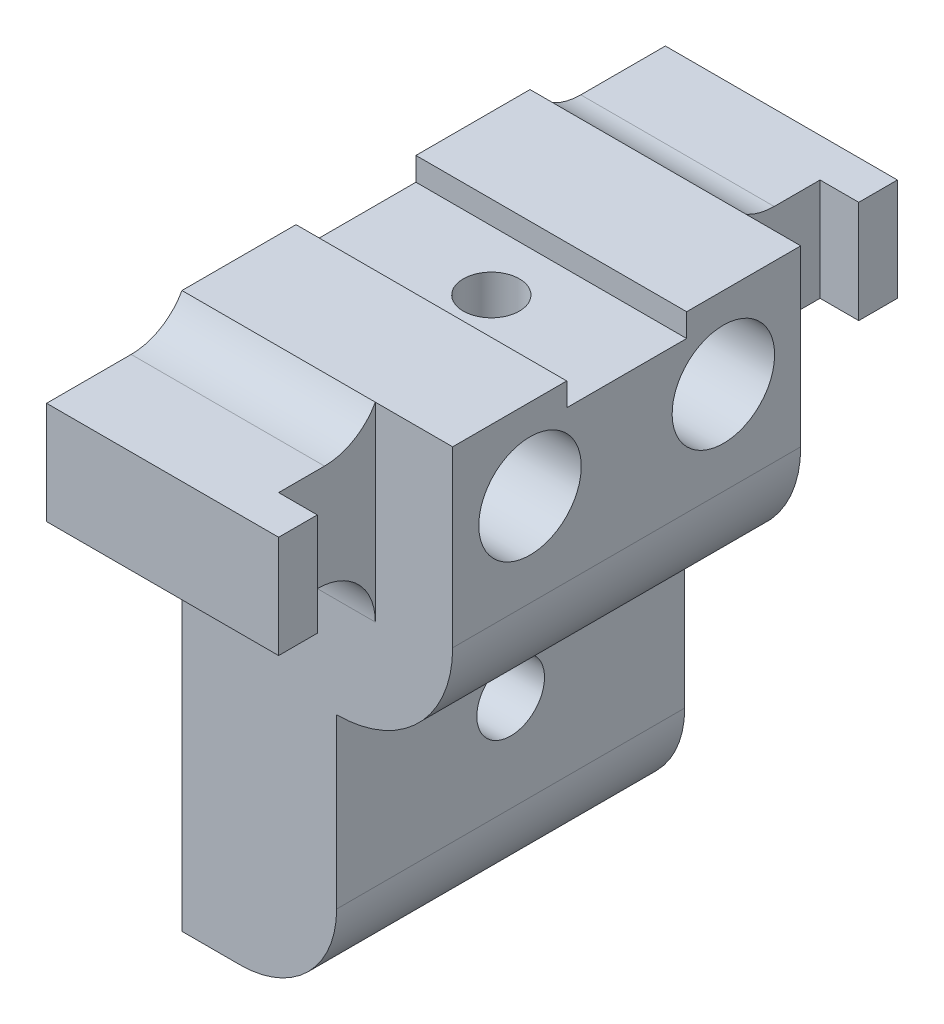
SolidWorks part; units mm, degrees
ref_plane "Front Plane" through (0, 0, 0) normal (0, 0, 1) x (1, 0, 0)
ref_plane "Top Plane" through (0, 0, 0) normal (0, 1, 0) x (1, 0, 0)
ref_plane "Right Plane" through (0, 0, 0) normal (1, 0, 0) x (0, 0, -1)
sketch "Sketch1" plane through (0, 0, 0) normal (0, 0, 1) x (1, 0, 0)
  line L1 (0, 0) -> (8, 0)
  line L2 (0, 0) -> (0, -28.7)
  line L3 (0, -28.7) -> (8, -28.7)
  line L4 (8, 0) -> (8, -28.7)
  line L5 (8, 0) -> (14, 0)
  line L6 (8, 0) -> (8, -15)
  line L7 (8, -15) -> (14, -15)
  line L8 (14, 0) -> (14, -15)
  dimension "D1" = 28.7
  dimension "D2" = 8
  dimension "D3" = 6
  dimension "D4" = 15
extrude "Boss-Extrude1" add sketch "Sketch1" along normal mid plane 18 contours L8 L5 L4 L7 | L4 L1 L2 L3 region at (4, -14.35, 0) region at (11, -7.5, 0)
sketch "Sketch2" plane through (14, 0, 0) normal (1, 0, 0) x (0, 0, -1)
  line L0 (0, 0) -> (0, -10.4868) construction
  line L1 (-9, 0) -> (9, 0) construction
  circle A0 centre (5, -4.2) radius 2.65
  circle A1 centre (-5, -4.2) radius 2.65
  dimension "D1" = 5.3
  dimension "D2" = 4.2
  dimension "D3" = 5
extrude "Cut-Extrude1" cut sketch "Sketch2" against normal through all
sketch "Sketch5" plane through (0, 0, 9) normal (0, 0, 1) x (1, 0, 0)
  line L0 (0, -6.85) -> (14, -6.85) construction
  line L1 (0, -1.55) -> (10, -1.55)
  line L2 (0, -1.55) -> (0, -6.85)
  line L3 (0, -6.85) -> (10, -6.85)
  line L4 (10, -1.55) -> (10, -6.85)
  dimension "D1" = 10
extrude "Boss-Extrude4" add sketch "Sketch5" along normal blind 5
sketch "Sketch6" plane through (0, 0, 14) normal (0, 0, 1) x (1, 0, 0)
  line L0 (0, -6.85) -> (10, -6.85) construction
  line L1 (0, -1.55) -> (12, -1.55)
  line L2 (0, -1.55) -> (0, -6.85)
  line L3 (0, -6.85) -> (12, -6.85)
  line L4 (12, -1.55) -> (12, -6.85)
  dimension "D1" = 12
extrude "Boss-Extrude5" add sketch "Sketch6" along normal blind 2
mirror "Mirror2" about plane through (0, 0, 0) normal (0, 0, 1) of "Boss-Extrude5", "Boss-Extrude4"
sketch "Sketch7" plane through (0, 0, 0) normal (0, 1, 0) x (1, 0, 0)
  line L0 (0, -9) -> (0, 9) construction
  line L1 (0, 3.1) -> (14, 3.1)
  line L2 (0, 3.1) -> (0, -3.1)
  line L3 (0, -3.1) -> (14, -3.1)
  line L4 (14, 3.1) -> (14, -3.1)
  line L5 (14, -9) -> (14, 9) construction
  point P9 (0, 0)
  dimension "D1" = 6.2
extrude "Cut-Extrude2" cut sketch "Sketch7" against normal blind 1.2
sketch "Sketch8" plane through (0, -1.2, 0) normal (0, 1, 0) x (1, 0, 0)
  circle A0 centre (7, 0) radius 1.45
  dimension "D1" = 2.9
  dimension "D2" = 7
extrude "Cut-Extrude3" cut sketch "Sketch8" against normal blind 8
sketch "Sketch9" plane through (0, 0, 0) normal (-1, 0, 0) x (0, 0, 1)
  line L0 (-9, -6.85) -> (-9, -28.7) construction
  line L1 (9, -28.7) -> (-9, -28.7) construction
  line L2 (9, -28.7) -> (9, -8.7) construction
  line L3 (9, -8.7) -> (-9, -8.7) construction
  line L4 (-9, -28.7) -> (-9, -8.7) construction
  line L5 (9, -8.7) -> (-9, -28.7) construction
  circle A0 centre (0, -18.7) radius 1.75
  dimension "D2" = 3.5
  dimension "D1" = 20
extrude "Cut-Extrude4" cut sketch "Sketch9" against normal through all and the other way through all
fillet "Fillet1" radius 5 1 edges at (8, -28.7, 0)
fillet "Fillet2" radius 6 1 edges at (14, -15, 0)
fillet "Fillet3" radius 3 4 edges at (5, -1.55, -9) (5, -6.85, -9) (5, -1.55, 9) (5, -6.85, 9)
